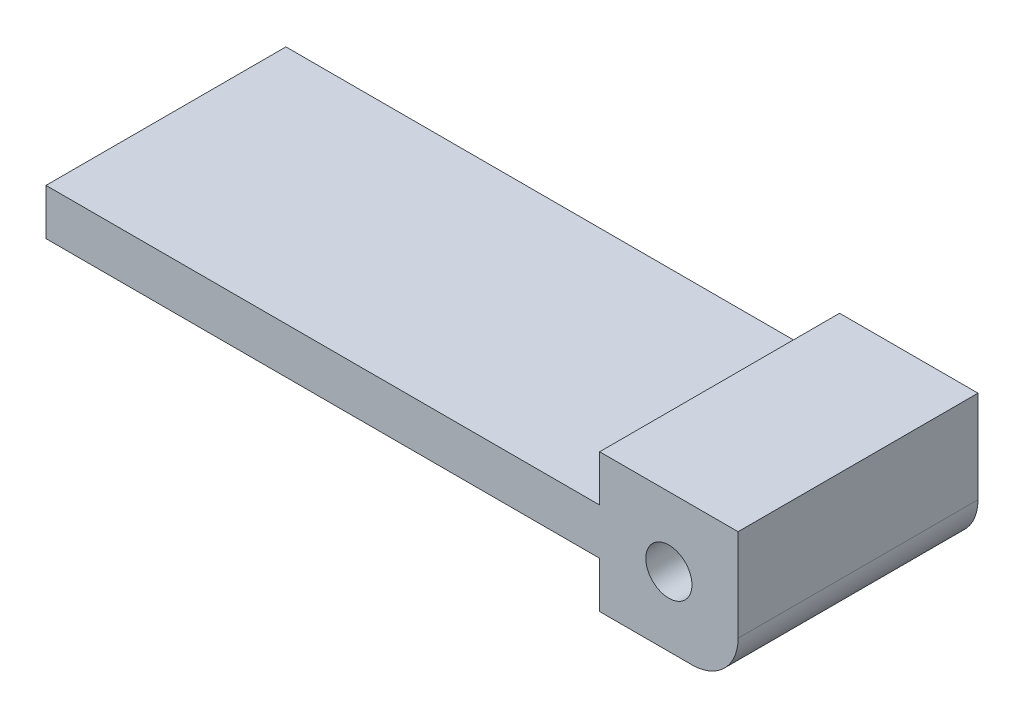
SolidWorks part; units mm, degrees
ref_plane "Ebene vorne" through (0, 0, 0) normal (0, 0, 1) x (1, 0, 0)
ref_plane "Ebene oben" through (0, 0, 0) normal (0, 1, 0) x (1, 0, 0)
ref_plane "Ebene rechts" through (0, 0, 0) normal (1, 0, 0) x (0, 0, -1)
sketch "Skizze1" plane through (0, 0, 0) normal (0, 0, 1) x (1, 0, 0)
  line L0 (0, 0) -> (-15, 0)
  line L1 (-15, 0) -> (-15, 5)
  line L2 (-15, 5) -> (-75, 5)
  line L3 (-75, 5) -> (-75, 10)
  line L4 (-75, 10) -> (-15, 10)
  line L5 (-15, 10) -> (-15, 15)
  line L6 (-15, 15) -> (0, 15)
  line L7 (0, 15) -> (0, 0)
  dimension "D1" = 15
  dimension "D2" = 5
  dimension "D3" = 60
  dimension "D4" = 5
  dimension "D5" = 5
  dimension "D6" = 15
extrude "Aufsatz-Linear austragen1" add sketch "Skizze1" along normal blind 26
sketch "Skizze2" plane through (0, 0, 26) normal (0, 0, 1) x (1, 0, 0)
  line L0 (-15, 0) -> (0, 0) construction
  line L1 (0, 0) -> (0, 15) construction
  circle A0 centre (-7.5, 7.5) radius 2.5
  point P2 (-7.5, 0)
  dimension "D1" = 5
  dimension "D2" = 7.5
  dimension "D3" = 7.5
extrude "Schnitt-Linear austragen1" cut sketch "Skizze2" against normal through all
fillet "Verrundung1" radius 5 1 edges at (0, 0, 13)
